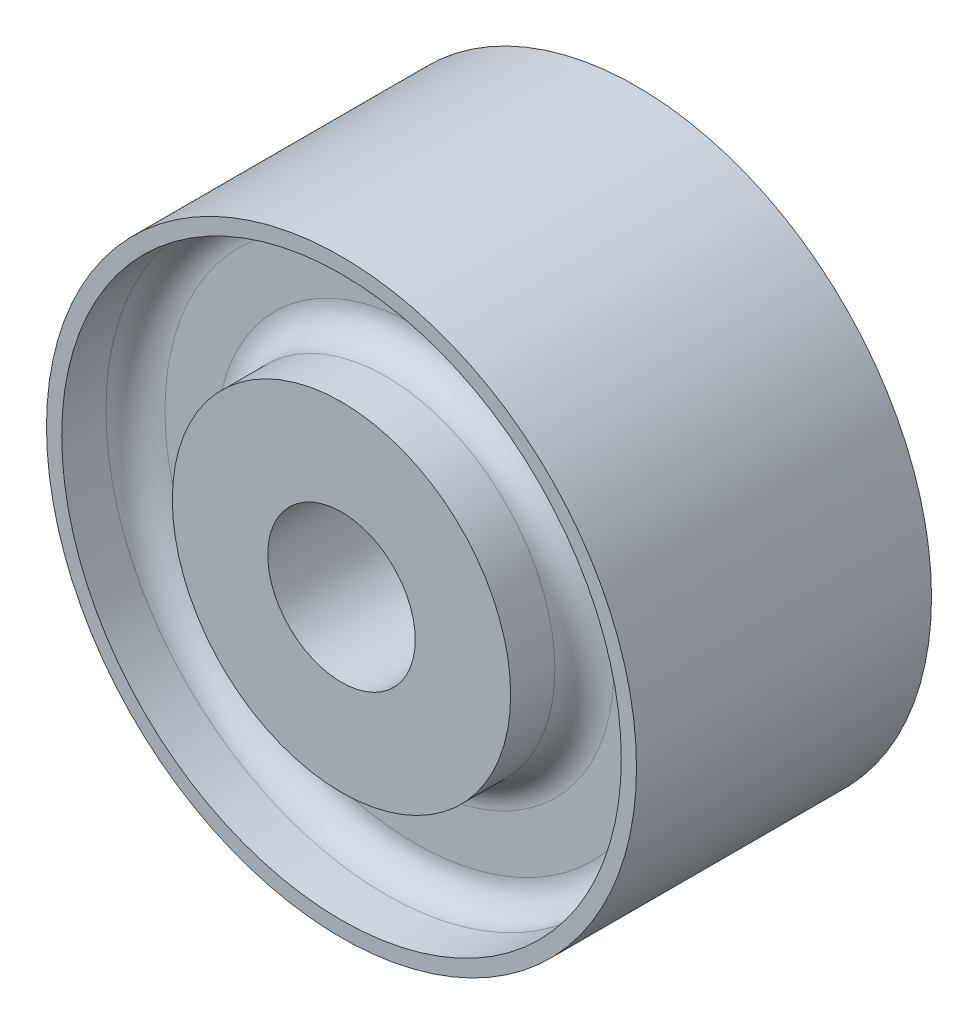
SolidWorks part; units mm, degrees
ref_plane "Front Plane" through (0, 0, 0) normal (0, 0, 1) x (1, 0, 0)
ref_plane "Top Plane" through (0, 0, 0) normal (0, 1, 0) x (1, 0, 0)
ref_plane "Right Plane" through (0, 0, 0) normal (1, 0, 0) x (0, 0, -1)
sketch "Sketch1" plane through (0, 0, 0) normal (0, 0, 1) x (1, 0, 0)
  circle A0 centre (0, 0) radius 50.8
  point P3 (-217.7978, -25.2539)
extrude "Boss-Extrude1" add sketch "Sketch1" along normal blind 25.4 and the other way blind 25.4 contours A0
sketch "Sketch3" plane through (0, 0, 25.4) normal (0, 0, 1) x (1, 0, 0)
  circle A0 centre (0, 0) radius 12.7
extrude "Cut-Extrude2" cut sketch "Sketch3" against normal through all contours A0
sketch "Sketch4" plane through (0, 0, 25.4) normal (0, 0, 1) x (1, 0, 0)
  circle A0 centre (0, 0) radius 38.1
ref_plane "Plane1" through (0, 0, 0) normal (1, 0, 0) x (0, 0, -1)
sketch "Sketch7" plane through (0, 0, 0) normal (1, 0, 0) x (0, 0, -1)
  line L0 (-25.4, 38.1) -> (-25.4, -38.1) construction
  line L1 (-25.4, 48.177) -> (-17.78, 48.177)
  line L2 (-25.4, 48.177) -> (-25.4, 29.127)
  line L3 (-25.4, 29.127) -> (-17.78, 29.127)
  line L4 (-12.7, 43.097) -> (-12.7, 34.207)
  line L5 (-25.4, 48.177) -> (-12.7, 29.127) construction
  line L6 (-25.4, 29.127) -> (-12.7, 48.177) construction
  arc A0 (-12.7, 43.097) -> (-17.78, 48.177) centre (-17.78, 43.097) ccw
  arc A1 (-12.7, 34.207) -> (-17.78, 29.127) centre (-17.78, 34.207) cw
  point P0 (-19.05, 38.652)
  dimension "D3" = 5.08
  dimension "D4" = 5.08
  dimension "D1" = 19.05
  dimension "D2" = 12.7
  dimension "D5" = 29.127
sweep "Cut-Sweep1" cut profiles "Sketch7" path "Sketch4"
mirror "Mirror1" about plane through (0, 0, 0) normal (0, 0, 1) of "Cut-Sweep1"
